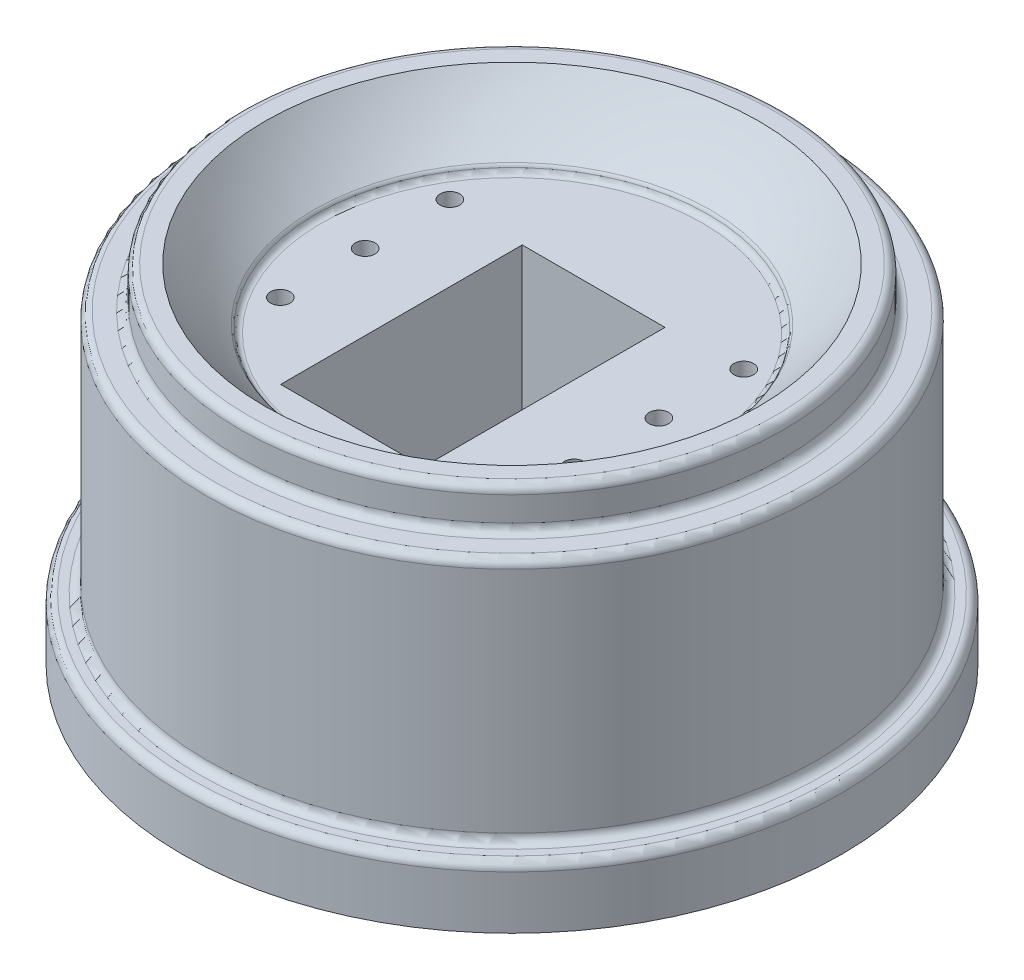
SolidWorks part; units mm, degrees
ref_plane "Front Plane" through (0, 0, 0) normal (0, 0, 1) x (1, 0, 0)
ref_plane "Top Plane" through (0, 0, 0) normal (0, 1, 0) x (1, 0, 0)
ref_plane "Right Plane" through (0, 0, 0) normal (1, 0, 0) x (0, 0, -1)
sketch "Sketch1" plane through (0, 0, 0) normal (0, 0, 1) x (1, 0, 0)
  line L0 (-46.7291, -58.6097) -> (46.7291, -58.6097) construction
  line L1 (0, -58.6097) -> (46.7291, -58.6097)
  line L2 (60.5301, -43.8597) -> (66.5301, -43.8597)
  line L3 (58.5739, -43.8597) -> (-58.5739, -43.8597) construction
  line L4 (0, -128.8597) -> (0, -58.6097)
  line L5 (66.5301, -43.8597) -> (66.5301, -53.8597)
  line L6 (66.5301, -53.8597) -> (74.75, -53.8597)
  line L7 (74.75, -53.8597) -> (74.75, -113.8597)
  line L8 (74.75, -113.8597) -> (80.75, -113.8597)
  line L9 (80.75, -113.8597) -> (80.75, -128.8597)
  line L10 (80.75, -128.8597) -> (0, -128.8597)
  arc A0 (46.7291, -58.6097) -> (48.1773, -57.5003) centre (46.7291, -57.1097) ccw construction
  arc A1 (48.6493, -56.7521) -> (48.1773, -57.5003) centre (49.6256, -57.891) ccw construction
  arc A2 (48.6493, -56.7521) -> (-48.6493, -56.7521) centre (0, 0) ccw construction
  arc A3 (46.7291, -58.6097) -> (48.1773, -57.5003) centre (46.7291, -57.1097) ccw
  arc A4 (48.6493, -56.7521) -> (48.1773, -57.5003) centre (49.6256, -57.891) ccw
  arc A5 (48.6493, -56.7521) -> (60.5301, -43.8597) centre (0, 0) ccw
  point P17 (80.75, -121.3597)
  point P21 (74.75, 0)
  point P22 (0, 0)
  point P23 (0, 0)
  dimension "D1" = 6
  dimension "D2" = 10
  dimension "D3" = 6
  dimension "D4" = 15
  dimension "D5" = 85
revolve "Revolve1" add sketch "Sketch1" angle 360 about L4
fillet "Fillet1" radius 2 3 edges at (0, -113.8597, -80.75) (0, -53.8597, -74.75) (0, -43.8597, -66.5301)
fillet "Fillet2" radius 2 2 edges at (0, -113.8597, -74.75) (0, -53.8597, -66.5301)
sketch "Sketch2" plane through (0, -128.8597, 0) normal (0, -1, 0) x (1, 0, 0)
  line L0 (31, 15.8) -> (-31, 15.8)
  line L1 (-31, -47) -> (31, -47)
  line L2 (-31, -47) -> (-31, 47)
  line L3 (-31, 47) -> (31, 47)
  line L4 (31, -47) -> (31, 47)
  line L5 (-31, -47) -> (31, 47) construction
  line L6 (-31, 47) -> (31, -47) construction
  line L8 (-31, -47) -> (31, -47)
  line L9 (-31, -47) -> (-31, -15.8)
  line L10 (-31, -15.8) -> (31, -15.8)
  line L11 (31, -47) -> (31, -15.8)
  point P0 (0, 0)
  dimension "D1" = 94
  dimension "D2" = 62
  dimension "D3" = 31.2
  dimension "D4" = 31.2
extrude "Cut-Extrude1" cut sketch "Sketch2" against normal blind 33 contours L0 L4 L3 L2 region at (0, -128.8597, 31.4)
sketch "Sketch3" plane through (0, -128.8597, 0) normal (0, -1, 0) x (1, 0, 0)
  line L1 (41, 57) -> (-41, 57)
  line L2 (41, 57) -> (41, -57)
  line L3 (41, -57) -> (-41, -57)
  line L4 (-41, 57) -> (-41, -57)
  line L5 (41, 57) -> (-41, -57) construction
  line L6 (41, -57) -> (-41, 57) construction
  point P0 (0, 0)
  dimension "D1" = 114
  dimension "D2" = 82
extrude "Cut-Extrude2" cut sketch "Sketch3" against normal blind 3
fillet "Fillet3" radius 10 4 edges at (-41, -127.3597, 57) (-41, -127.3597, -57) (41, -127.3597, -57) (41, -127.3597, 57)
extrude "Cut-Extrude3" cut sketch "Sketch2<3>" against normal blind 16 from surface contours L10 L2 L1 L4 region at (0, -128.8597, -31.4) starting at face at (0, -125.8597, 31.4)
sketch "Sketch2<3>" plane through (0, -128.8597, 0) normal (0, -1, 0) x (1, 0, 0) same geometry as "Sketch2"
extrude "Cut-Extrude4" cut sketch "Sketch2<4>" against normal up to surface (33 mm away) contours L2 L10 L4 L0 region at (0, -128.8597, 0) up to face at (0, -95.8597, 31.4)
sketch "Sketch2<4>" plane through (0, -128.8597, 0) normal (0, -1, 0) x (1, 0, 0) same geometry as "Sketch2"
sketch "Sketch6" plane through (0, -95.8597, 0) normal (0, -1, 0) x (-1, 0, 0)
  line L1 (17.5, 20) -> (-17.5, 20)
  line L2 (17.5, 20) -> (17.5, -39.2)
  line L3 (17.5, -39.2) -> (-17.5, -39.2)
  line L4 (-17.5, 20) -> (-17.5, -39.2)
  line L5 (0, 0) -> (0, 20) construction
  dimension "D1" = 39.2
  dimension "D2" = 35
  dimension "D3" = 20
extrude "Cut-Extrude5" cut sketch "Sketch6" against normal up to next and the other way up to next
sketch "Sketch8" plane through (0, -128.8597, 0) normal (0, -1, 0) x (1, 0, 0)
  line L0 (0, 0) -> (0, -58.5739) construction
  line L1 (-36, 0) -> (36, 0) construction
  line L2 (0, 0) -> (36, 20.7846) construction
  line L3 (0, 0) -> (36, -20.7846) construction
  line L4 (0, 0) -> (-36, -20.7846) construction
  line L5 (0, 0) -> (-36, 20.7846) construction
  line L6 (31, -47) -> (31, 47) construction
  line L7 (31, -47) -> (31, 47) construction
  line L8 (41, 0) -> (31, 0) construction
  line L9 (41, -47) -> (41, 47) construction
  circle A2 centre (0, 0) radius 46.7291 construction
  circle A3 centre (0, 0) radius 46.7291 construction
  point P17 (0, 0)
  point P18 (36, 0)
  point P19 (36, -17.7312)
  point P20 (36, 6.6151)
  point P21 (0, 0)
  dimension "D1" = 60
hole_wizard "CBORE for M4 Hex Socket Head Cap Screw1" positions "Sketch9" profile "Sketch11" counterbore size "M4" standard "ISO" end condition up to next
sketch "Sketch9" plane through (0, -128.8597, 0) normal (0, -1, 0) x (-1, 0, 0)
  point P0 (-36, 0)
  point P3 (-36, -20.7846)
  point P6 (-36, 20.7846)
  point P9 (36, 20.7846)
  point P12 (36, 0)
  point P15 (36, -20.7846)
sketch "Sketch11" plane through (36, -128.8597, 0) normal (1, 0, 0) x (0, 0, -1)
  line L0 (0, 0) -> (0, 70.25)
  line L1 (0, 70.25) -> (2.4, 70.25)
  line L3 (2.4, 70.25) -> (2.4, 7.4)
  line L4 (2.4, 7.4) -> (4, 7.4)
  line L5 (4, 7.4) -> (4, 0)
  line L7 (4, 0) -> (0, 0)
  line L11 (0, -6.35) -> (0, 107.95) construction
  dimension "Thru Hole Dia." = 4.8
  dimension "Thru Hole Depth" = 70.25
  dimension "C'Bore Dia." = 8
  dimension "C'Bore Depth" = 7.4
